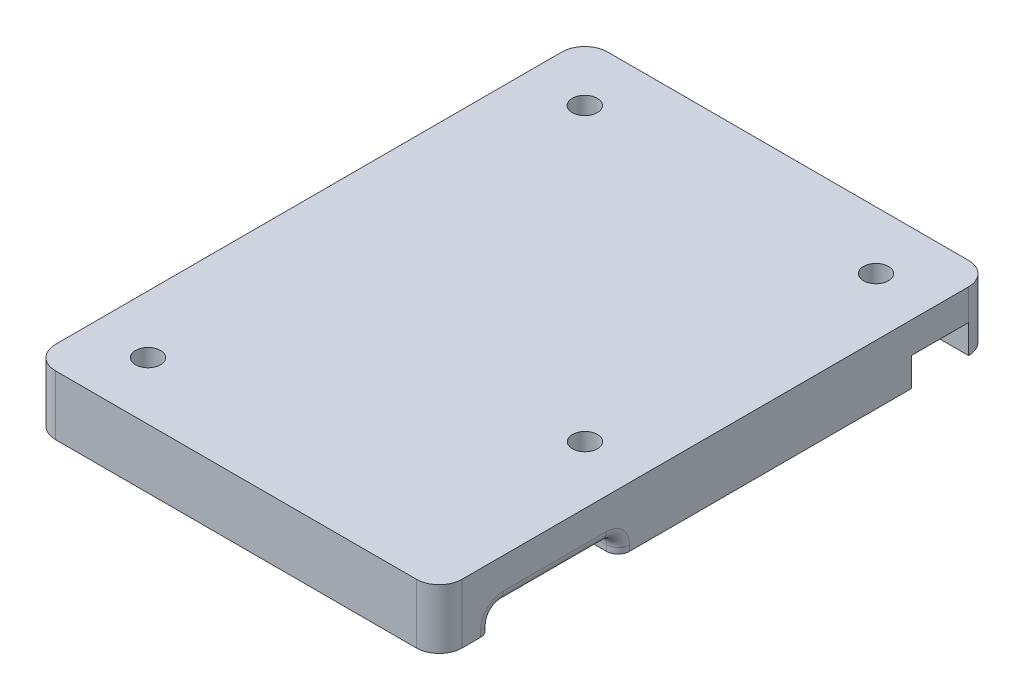
SolidWorks part; units mm, degrees
ref_plane "Front Plane" through (0, 0, 0) normal (0, 0, 1) x (1, 0, 0)
ref_plane "Top Plane" through (0, 0, 0) normal (0, 1, 0) x (1, 0, 0)
ref_plane "Right Plane" through (0, 0, 0) normal (1, 0, 0) x (0, 0, -1)
sketch "Sketch1" plane through (0, 0, 0) normal (0, 1, 0) x (1, 0, 0)
  line L1 (-7.3177, 13.3633) -> (23.1823, 13.3633)
  line L2 (-7.3177, 13.3633) -> (-7.3177, -29.8367)
  line L3 (-7.3177, -29.8367) -> (23.1823, -29.8367)
  line L4 (23.1823, 13.3633) -> (23.1823, -29.8367)
  line L5 (-7.8177, 13.8633) -> (23.6823, 13.8633)
  line L6 (-7.8177, 13.8633) -> (-7.8177, -30.3367)
  line L7 (-7.8177, -30.3367) -> (23.6823, -30.3367)
  line L8 (23.6823, 13.8633) -> (23.6823, -30.3367)
  line L9 (-9.8177, 15.8633) -> (25.6823, 15.8633)
  line L10 (-9.8177, 15.8633) -> (-9.8177, -32.3367)
  line L11 (-9.8177, -32.3367) -> (25.6823, -32.3367)
  line L12 (25.6823, 15.8633) -> (25.6823, -32.3367)
  circle A4 centre (20.6423, 10.8233) radius 1.09
  circle A5 centre (-4.7777, 10.8233) radius 1.09
  circle A6 centre (-4.7777, -27.2967) radius 1.09
  circle A7 centre (20.6423, -14.5767) radius 1.09
  dimension "D3" = 2.54
  dimension "D4" = 2.54
  dimension "D5" = 2.18
  dimension "D6" = 2.18
  dimension "D9" = 2.18
  dimension "D12" = 2.18
  dimension "D1" = 43.2
  dimension "D2" = 30.5
  dimension "D7" = 2.54
  dimension "D8" = 2.54
  dimension "D10" = 2.54
  dimension "D11" = 2.54
  dimension "D13" = 2.54
  dimension "D14" = 25.4
  dimension "D15" = 0.5
  dimension "D16" = 0.5
  dimension "D17" = 0.5
  dimension "D18" = 0.5
  dimension "D19" = 2
  dimension "D20" = 2
  dimension "D21" = 2
  dimension "D22" = 2
extrude "Boss-Extrude2" add sketch "Sketch1" along normal blind 5.2 contours L9 L12 L11 L10 | A7 | A4 | A5 | A6
extrude "Cut-Extrude1" cut sketch "Sketch1<4>" along normal blind 1.6 contours L5 L8 L7 L6
sketch "Sketch1<4>" plane through (0, 0, 0) normal (0, 1, 0) x (1, 0, 0) same geometry as "Sketch1"
sketch "Sketch3" plane through (0, 1.6, 0) normal (0, -1, 0) x (1, 0, 0)
  line L0 (-2.7377, -13.8633) -> (18.6023, -13.8633)
  line L5 (18.6023, -13.8633) -> (18.6023, -8.7833)
  line L6 (18.6023, -8.7833) -> (23.6823, -8.7833)
  line L7 (18.6023, 14.5767) -> (23.6823, 14.5767) construction
  line L12 (18.6023, 17.1167) -> (18.6023, 12.0367)
  line L13 (18.6023, 12.0367) -> (23.6823, 12.0367)
  line L18 (-7.8177, -13.8633) -> (-7.8177, -8.7833) construction
  line L19 (-7.8177, -13.8633) -> (-7.8177, 30.3367) construction
  line L20 (-7.8177, -13.8633) -> (-2.7377, -13.8633) construction
  line L21 (-7.8177, -13.8633) -> (23.6823, -13.8633) construction
  line L22 (-2.7377, -13.8633) -> (-2.7377, -8.7833)
  line L23 (-2.7377, -8.7833) -> (-7.8177, -8.7833)
  line L24 (23.6823, -13.8633) -> (23.6823, -8.7833) construction
  line L25 (23.6823, -13.8633) -> (23.6823, 30.3367) construction
  line L26 (23.6823, -13.8633) -> (18.6023, -13.8633) construction
  line L27 (23.6823, 12.0367) -> (23.6823, -8.7833)
  line L28 (18.6023, 17.1167) -> (23.6823, 17.1167)
  line L29 (23.6823, 17.1167) -> (23.6823, 30.3367)
  line L30 (-7.8177, 30.3367) -> (-2.7377, 30.3367) construction
  line L31 (-7.8177, 30.3367) -> (23.6823, 30.3367) construction
  line L32 (-7.8177, 30.3367) -> (-7.8177, 25.2567) construction
  line L33 (23.6823, 30.3367) -> (-2.7377, 30.3367)
  line L34 (-2.7377, 30.3367) -> (-2.7377, 25.2567)
  line L35 (-2.7377, 25.2567) -> (-7.8177, 25.2567)
  line L36 (-7.8177, 25.2567) -> (-7.8177, -8.7833)
  point P20 (18.6023, 14.5767)
  dimension "D1" = 5.08
  dimension "D2" = 5.08
  dimension "D3" = 5.08
  dimension "D4" = 5.08
  dimension "D5" = 5.08
  dimension "D6" = 5.08
  dimension "D7" = 5.08
  dimension "D8" = 5.08
extrude "Cut-Extrude2" cut sketch "Sketch3" against normal blind 2
sketch "Sketch6" plane through (0, 3.6, 0) normal (0, -1, 0) x (1, 0, 0)
  line L5 (18.6023, -13.8633) -> (-2.7377, -13.8633)
  line L6 (18.6023, -13.8633) -> (18.6023, -5.3633)
  line L7 (18.6023, -5.3633) -> (-2.7377, -5.3633)
  line L8 (-2.7377, -13.8633) -> (-2.7377, -5.3633)
  dimension "D1" = 21.34
  dimension "D2" = 8.5
extrude "Cut-Extrude5" cut sketch "Sketch6" against normal blind 1
sketch "Sketch4" plane through (0, 0, 0) normal (0, -1, 0) x (1, 0, 0)
  line L11 (25.6823, -15.8633) -> (25.6823, 32.3367) construction
  line L12 (25.6823, -13.8633) -> (23.6823, -13.8633)
  line L13 (25.6823, -13.8633) -> (25.6823, -8.8633)
  line L14 (25.6823, -8.8633) -> (23.6823, -8.8633)
  line L15 (23.6823, -13.8633) -> (23.6823, -8.8633)
  line L16 (23.6823, -13.8633) -> (23.6823, 30.3367) construction
  line L17 (-9.8177, -15.8633) -> (25.6823, -15.8633) construction
  line L18 (-7.8177, -13.8633) -> (-7.8177, 30.3367) construction
  line L19 (-7.8177, -13.8633) -> (-9.8177, -13.8633)
  line L20 (-7.8177, -13.8633) -> (-7.8177, -8.8633)
  line L21 (-7.8177, -8.8633) -> (-9.8177, -8.8633)
  line L22 (-9.8177, -13.8633) -> (-9.8177, -8.8633)
  line L23 (-9.8177, -15.8633) -> (-9.8177, 32.3367) construction
  dimension "D1" = 5
  dimension "D2" = 2
  dimension "D3" = 5
  dimension "D4" = 2
extrude "Cut-Extrude3" cut sketch "Sketch4" against normal blind 2.5
sketch "Sketch5" plane through (25.6823, 0, 0) normal (1, 0, 0) x (0, 0, -1)
  line L7 (8.8633, 0) -> (-32.3367, 0) construction
  line L8 (-27.7367, 0) -> (-16.7367, 0)
  line L9 (-27.7367, 0) -> (-27.7367, 1.5)
  line L10 (-27.7367, 1.5) -> (-16.7367, 1.5)
  line L11 (-16.7367, 0) -> (-16.7367, 1.5)
  line L12 (-32.3367, 5.2) -> (-32.3367, 0) construction
  dimension "D1" = 4.6
  dimension "D2" = 11
  dimension "D3" = 1.5
extrude "Cut-Extrude4" cut sketch "Sketch5" against normal blind 2
fillet "Fillet1" radius 2 4 edges at (25.6823, 2.6, -15.8633) (-9.8177, 2.6, -15.8633) (-9.8177, 2.6, 32.3367) (25.6823, 2.6, 32.3367)
fillet "Fillet3" radius 2.54 5 edges at (18.6023, 2.6, -8.7833) (-2.7377, 2.6, -8.7833) (-2.7377, 2.6, 25.2567) (18.6023, 2.6, 12.0367) (18.6023, 2.6, 17.1167)
fillet "Fillet4" radius 1 2 edges at (24.6823, 1.5, 27.7367) (24.6823, 1.5, 16.7367)
fillet "Fillet2" radius 1 5 edges at (25.6823, 0.25, 27.7367) (25.6823, 0.25, 16.7367) (25.6823, 1.5, 22.2367) (25.6823, 1.2071, 17.0296) (25.6823, 1.2071, 27.4438)
